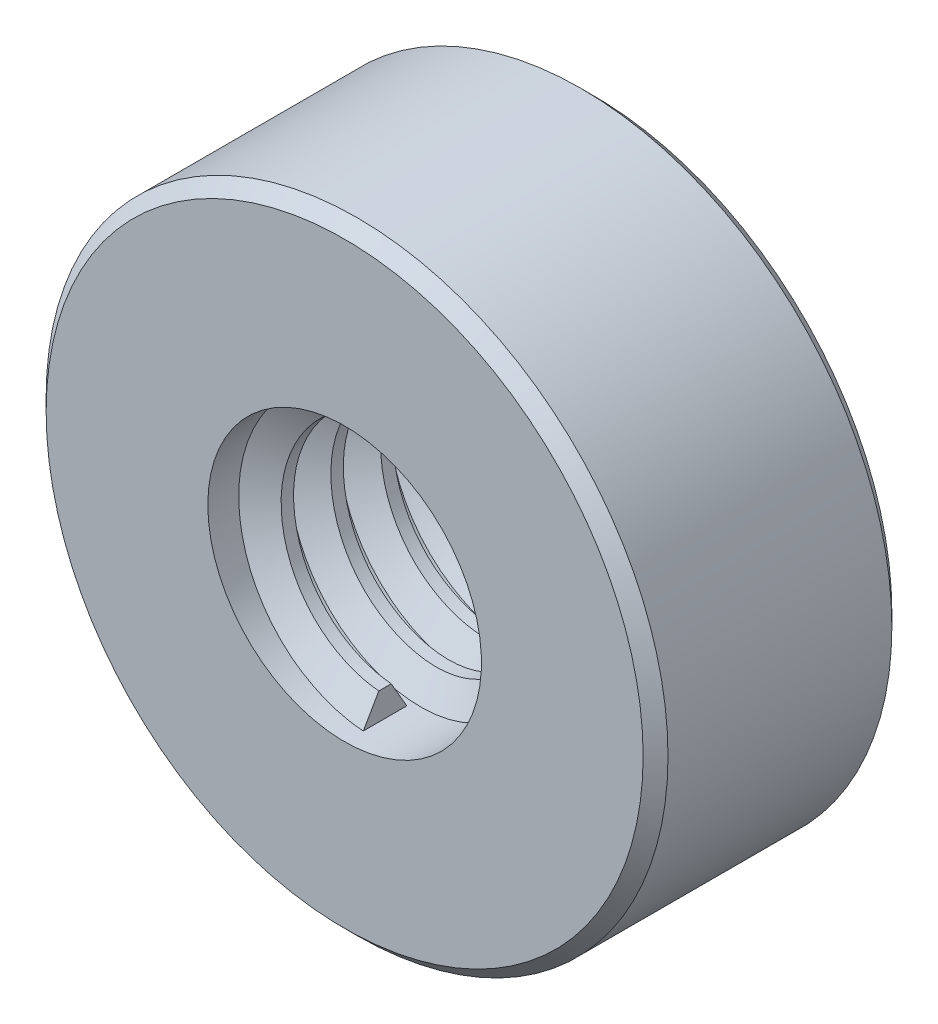
SolidWorks part; units mm, degrees
ref_plane "Спереди" through (0, 0, 0) normal (0, 0, 1) x (1, 0, 0)
ref_plane "Сверху" through (0, 0, 0) normal (0, 1, 0) x (1, 0, 0)
ref_plane "Справа" through (0, 0, 0) normal (1, 0, 0) x (0, 0, -1)
sketch "Эскиз1" plane through (0, 0, 0) normal (0, 0, 1) x (1, 0, 0)
  circle A0 centre (0, 0) radius 2.5
  dimension "D1" = 5
extrude "Бобышка-Вытянуть1" add sketch "Эскиз1" along normal blind 2
chamfer "Фаска2" distance 0.1 angle 45 2 edges at (2.5, 0, 0) (2.5, 0, 2)
hole_wizard "Отверстие с зазором M21" positions "Эскиз2" profile "Эскиз3" hole size "M2" standard "ISO" end condition through all
sketch "Эскиз2" plane through (0, 0, 0) normal (0, 0, -1) x (-1, 0, 0)
  point P0 (0, 0)
sketch "Эскиз3" plane through (0, 0, 0) normal (1, 0, 0) x (0, 1, 0)
  line L0 (0, 0) -> (0, 2)
  line L1 (0, 2) -> (1.1, 2)
  line L2 (1.1, 2) -> (1.1, 0)
  line L5 (1.1, 0) -> (0, 0)
  line L11 (0, -6.35) -> (0, 107.95) construction
  dimension "Диаметр сквозного отверстия" = 2.2
  dimension "Глубина сквозного отверстия" = 2
thread "Резьба1" pitch 0.4 method extrude profile "Профиль резьбы1" start angle 0, offset 0, length 1.5, pitch 0.4, diameter 2.2
ref_plane "Плоскость4" through (1.1, 0, 0) normal (0, -1, 0) x (1, 0, 0)
sketch "Профиль резьбы1" plane through (1.1, 0, 0) normal (0, -1, 0) x (1, 0, 0)
  line L0 (0, 0) -> (0, 0.4) construction
  line L11 (0, 0) -> (0, 0.35)
  line L12 (0, 0.35) -> (-0.2165, 0.225)
  line L13 (-0.2165, 0.225) -> (-0.2165, 0.125)
  line L15 (-0.2165, 0.125) -> (0, 0)
  line L17 (-0.2165, 0.175) -> (0, 0.175) construction
  point P2 (0, 0)
  dimension "Pitch" = 0.4
  dimension "Profile_Angle" = 60
  dimension "Profile_Land" = 0.1
  dimension "Profile_Height" = 0.2165
scale "Масштаб1" scale about centroid uniform scaling yes scale factor 2
